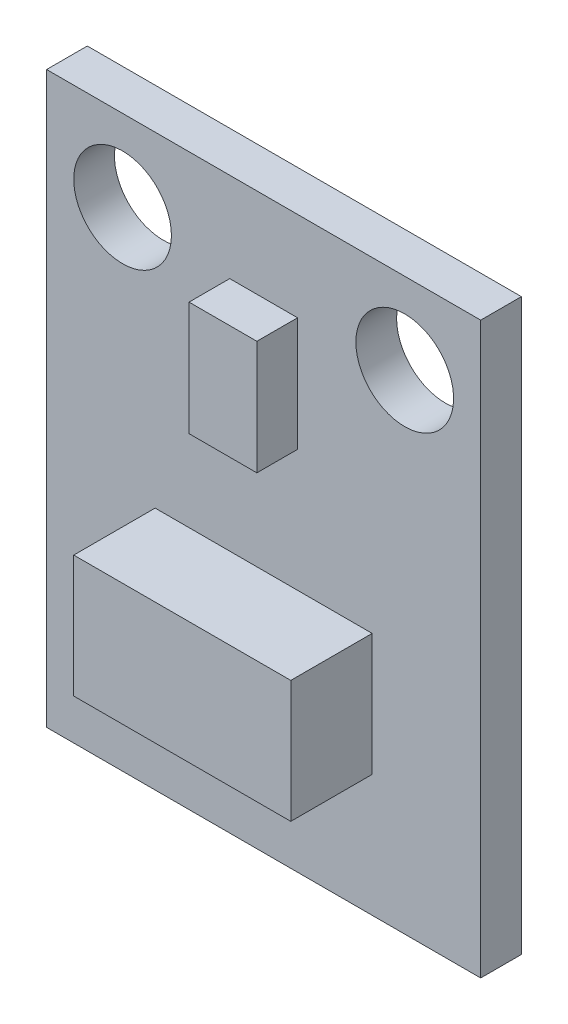
SolidWorks part; units mm, degrees
ref_plane "Front Plane" through (0, 0, 0) normal (0, 0, 1) x (1, 0, 0)
ref_plane "Top Plane" through (0, 0, 0) normal (0, 1, 0) x (1, 0, 0)
ref_plane "Right Plane" through (0, 0, 0) normal (1, 0, 0) x (0, 0, -1)
sketch "Sketch1" plane through (0, 0, 0) normal (0, 0, 1) x (1, 0, 0)
  line L0 (-5.2, 9.3) -> (-7, 9.3) construction
  line L1 (-8, 10.5) -> (8, 10.5)
  line L2 (-8, 10.5) -> (-8, -10.5)
  line L3 (-8, -10.5) -> (8, -10.5)
  line L4 (8, 10.5) -> (8, -10.5)
  line L5 (-8, 10.5) -> (8, -10.5) construction
  line L6 (-8, -10.5) -> (8, 10.5) construction
  line L7 (-7, 9.3) -> (-7, 7.5) construction
  line L8 (0, 0) -> (0, 10.5) construction
  circle A0 centre (-5.2, 7.5) radius 1.8
  circle A1 centre (5.2, 7.5) radius 1.8
  point P0 (0, 0)
  dimension "D3" = 3.6
  dimension "D1" = 16
  dimension "D2" = 21
  dimension "D4" = 1
  dimension "D5" = 1.2
extrude "Boss-Extrude1" add sketch "Sketch1" along normal blind 1.5
sketch "Sketch2" plane through (0, 0, 1.5) normal (0, 0, 1) x (1, 0, 0)
  line L0 (0, 0) -> (0, 5.1) construction
  line L1 (8, 10.5) -> (-8, 10.5) construction
  line L2 (-1.25, 7.2) -> (1.25, 7.2)
  line L3 (-1.25, 7.2) -> (-1.25, 3)
  line L4 (-1.25, 3) -> (1.25, 3)
  line L5 (1.25, 7.2) -> (1.25, 3)
  line L6 (-1.25, 7.2) -> (1.25, 3) construction
  line L7 (-1.25, 3) -> (1.25, 7.2) construction
  dimension "D1" = 4.2
  dimension "D2" = 2.5
  dimension "D3" = 7.5
extrude "Boss-Extrude2" add sketch "Sketch2" along normal blind 1.5
sketch "Sketch3" plane through (0, 0, 1.5) normal (0, 0, 1) x (1, 0, 0)
  line L0 (0, 0) -> (0, -3.75) construction
  line L1 (-4, -1.5) -> (4, -1.5)
  line L2 (-4, -1.5) -> (-4, -6)
  line L3 (-4, -6) -> (4, -6)
  line L4 (4, -1.5) -> (4, -6)
  line L5 (-4, -1.5) -> (4, -6) construction
  line L6 (-4, -6) -> (4, -1.5) construction
  line L7 (-8, -10.5) -> (8, -10.5) construction
  point P0 (0, -3.75)
  dimension "D1" = 8
  dimension "D2" = 4.5
  dimension "D3" = 9
extrude "Boss-Extrude3" add sketch "Sketch3" along normal blind 3
